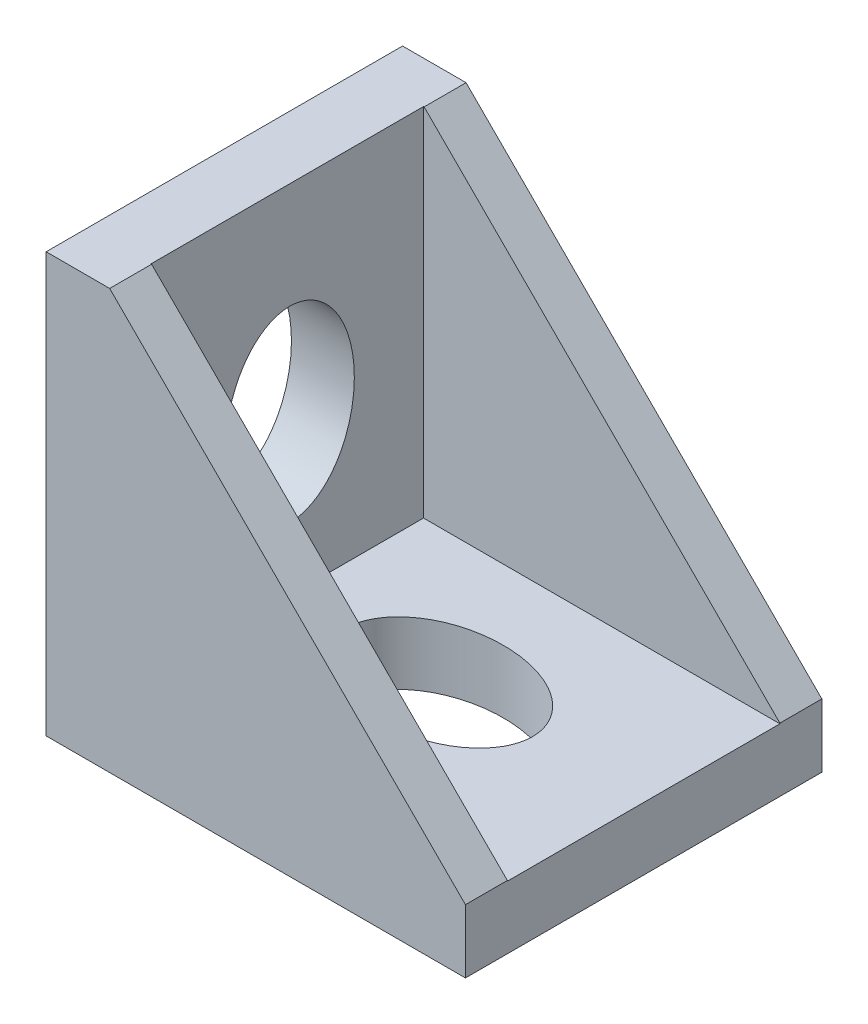
SolidWorks part; units mm, degrees
ref_plane "Front Plane" through (0, 0, 0) normal (0, 0, 1) x (1, 0, 0)
ref_plane "Top Plane" through (0, 0, 0) normal (0, 1, 0) x (1, 0, 0)
ref_plane "Right Plane" through (0, 0, 0) normal (1, 0, 0) x (0, 0, -1)
sketch "Sketch1" plane through (0, 0, 0) normal (0, 0, 1) x (1, 0, 0)
  line L0 (0, 0) -> (0, 20)
  line L1 (0, -55) -> (0, 55) construction
  line L2 (0, 20) -> (3.0294, 20)
  line L3 (3.0294, 20) -> (20, 3.0294)
  line L4 (20, 3.0294) -> (20, 0)
  line L5 (55, 0) -> (-55, 0) construction
  line L6 (20, 0) -> (0, 0)
  dimension "D1" = 24
  dimension "D2" = 20
  dimension "D3" = 20
extrude "Boss-Extrude1" add sketch "Sketch1" along normal blind 17
ref_plane "Plane1" through (0, 0, 2) normal (0, 0, 1) x (1, 0, 0)
sketch "Sketch2" plane through (0, 0, 2) normal (0, 0, 1) x (1, 0, 0)
  line L0 (0, -9.35) -> (0, 9.35) construction
  line L1 (3, 3) -> (20, 3)
  line L2 (3, 3) -> (3, 20)
  line L3 (3, 20) -> (20, 20)
  line L4 (20, 3) -> (20, 20)
  line L5 (9.35, 0) -> (-9.35, 0) construction
  dimension "D1" = 17
  dimension "D2" = 17
  dimension "D3" = 3
  dimension "D4" = 3
extrude "Cut-Extrude1" cut sketch "Sketch2" along normal blind 13
sketch "Sketch3" plane through (0, 0, 0) normal (0, 1, 0) x (1, 0, 0)
  line L2 (-11, 0) -> (11, 0) construction
  line L4 (0, -9.35) -> (0, 9.35) construction
  ellipse E0 centre (10.16, -8.425) end of major axis (14.63, -8.425) minor radius 3.075
  point P1 (0, 0)
  point P7 (0, 0)
  point P8 (0, 0)
  point P9 (0, 0)
  point P10 (0, 0)
  point P11 (0, 0)
  point P12 (0, 0)
  point P15 (0, 0)
  dimension "D1" = 5.35
  dimension "D3" = 5.69
extrude "Cut-Extrude2" cut sketch "Sketch3" along normal blind 13
sketch "Sketch5" plane through (0, 0, 0) normal (1, 0, 0) x (0, 0, -1)
  line L0 (-15, 20) -> (-2, 20) construction
  line L1 (0, 11) -> (0, -11) construction
  ellipse E0 centre (-8.375, 10.47) end of major axis (-8.375, 14.94) minor radius 3.075
  point P1 (0, 0)
  point P7 (0, 0)
  point P8 (0, 0)
  point P9 (0, 0)
  point P10 (0, 0)
  point P11 (0, 0)
  point P12 (0, 0)
  point P13 (-7.9943, 11.3065)
  point P14 (0, 0)
  point P15 (0, 0)
  dimension "D1" = 5.06
  dimension "D2" = 5.3
extrude "Cut-Extrude3" cut sketch "Sketch5" along normal blind 13
sketch "Sketch6" plane through (0, 0, 0) normal (1, 0, 0) x (0, 0, -1)
  line L0 (-17, 20) -> (0, 20) construction
  line L1 (-6.5, 19) -> (-10, 19)
  line L2 (-6.5, 19) -> (-6.5, 17.5)
  line L3 (-6.5, 17.5) -> (-10, 17.5)
  line L4 (-10, 19) -> (-10, 17.5)
  line L5 (-6.5, 3.5) -> (-10, 3.5)
  line L6 (-6.5, 3.5) -> (-6.5, 2)
  line L7 (-6.5, 2) -> (-10, 2)
  line L8 (-10, 3.5) -> (-10, 2)
  line L9 (9.35, 0) -> (-9.35, 0) construction
  line L10 (0, 11) -> (0, -11) construction
  dimension "D1" = 1.5
  dimension "D2" = 3.5
  dimension "D3" = 1
  dimension "D4" = 2
  dimension "D5" = 6.5
extrude "Boss-Extrude2" add sketch "Sketch6" against normal blind 1
fillet "Fillet1" radius 0.75 8 edges at (-0.5, 2, 6.5) (-0.5, 17.5, 6.5) (-0.5, 2, 10) (-0.5, 3.5, 10) (-0.5, 3.5, 6.5) (-0.5, 17.5, 10) (-0.5, 19, 10) (-0.5, 19, 6.5)
sketch "Sketch7" plane through (0, 0, 0) normal (0, 1, 0) x (1, 0, 0)
  line L0 (0, -9.3596) -> (0, 9.3596) construction
  line L1 (2, -6.5) -> (2, -10)
  line L2 (2, -6.5) -> (3.5, -6.5)
  line L3 (3.5, -6.5) -> (3.5, -10)
  line L4 (2, -10) -> (3.5, -10)
  line L5 (17.5, -6.5) -> (17.5, -10)
  line L6 (17.5, -6.5) -> (19, -6.5)
  line L7 (19, -6.5) -> (19, -10)
  line L8 (17.5, -10) -> (19, -10)
  line L9 (20, -15) -> (20, -2) construction
  line L11 (-11, 0) -> (11, 0) construction
  dimension "D1" = 1.5
  dimension "D2" = 3.5
  dimension "D3" = 2
  dimension "D4" = 1
  dimension "D5" = 6.5
extrude "Boss-Extrude3" add sketch "Sketch7" against normal blind 1
fillet "Fillet2" radius 0.75 8 edges at (3.5, -0.5, 6.5) (2, -0.5, 6.5) (2, -0.5, 10) (3.5, -0.5, 10) (17.5, -0.5, 10) (19, -0.5, 10) (17.5, -0.5, 6.5) (19, -0.5, 6.5)
